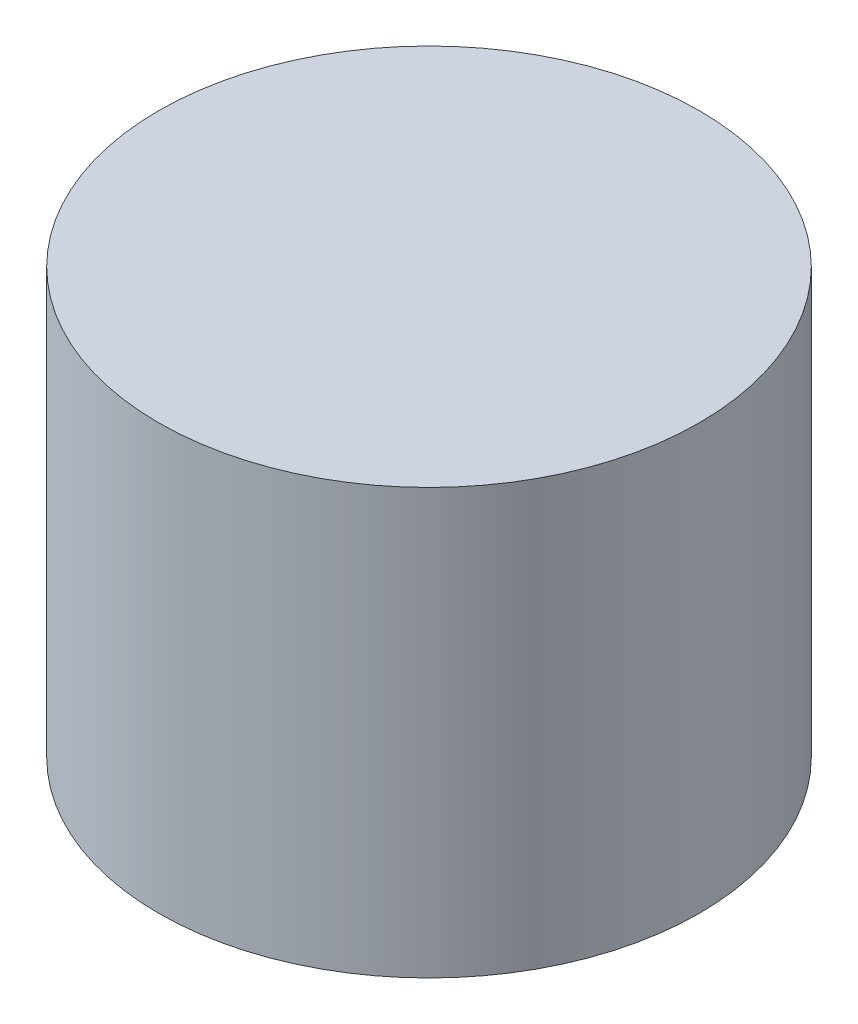
SolidWorks part; units mm, degrees
ref_plane "Front Plane" through (0, 0, 0) normal (0, 0, 1) x (1, 0, 0)
ref_plane "Top Plane" through (0, 0, 0) normal (0, 1, 0) x (1, 0, 0)
ref_plane "Right Plane" through (0, 0, 0) normal (1, 0, 0) x (0, 0, -1)
sketch "Sketch1" plane through (0, 0, 0) normal (0, 1, 0) x (1, 0, 0)
  circle A0 centre (0, 0) radius 35
  dimension "D1" = 70
extrude "Boss-Extrude1" add sketch "Sketch1" along normal blind 55
sketch "Sketch2" plane through (0, 55, 0) normal (0, 1, 0) x (1, 0, 0)
  line L0 (0, 35) -> (0, -35) construction
  line L1 (-35, 0) -> (35, 0) construction
  circle A0 centre (0, 0) radius 35 construction
sketch "Sketch3" plane through (0, 55, 0) normal (0, 1, 0) x (1, 0, 0)
  point P0 (0, 0)
